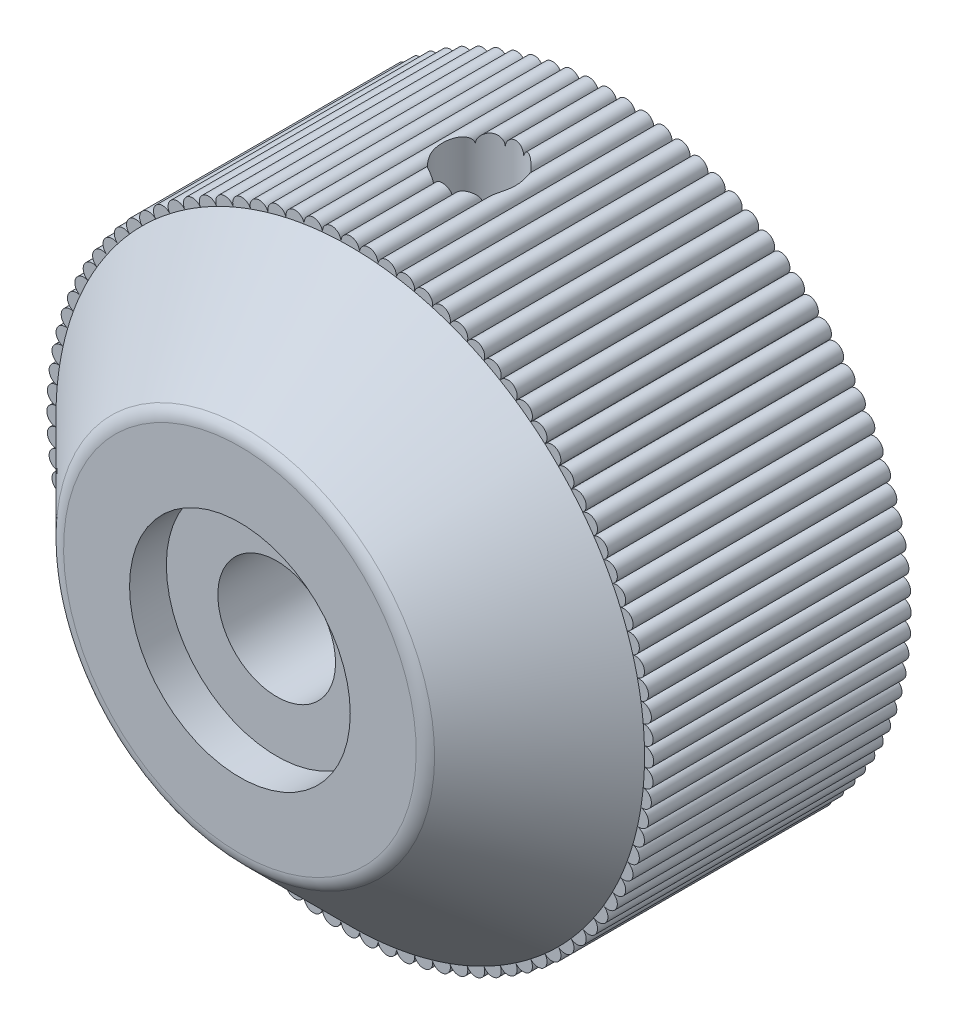
SolidWorks part; units mm, degrees
ref_plane "Front Plane" through (0, 0, 0) normal (0, 0, 1) x (1, 0, 0)
ref_plane "Top Plane" through (0, 0, 0) normal (0, 1, 0) x (1, 0, 0)
ref_plane "Right Plane" through (0, 0, 0) normal (1, 0, 0) x (0, 0, -1)
sketch "Main Body Sketch" plane through (0, 0, 0) normal (1, 0, 0) x (0, 0, -1)
  line L0 (0, 0) -> (-10, 0)
  line L1 (-10, 0) -> (-10, 5)
  line L2 (-10, 5) -> (-7, 8)
  line L4 (-7, 8) -> (0, 8)
  line L5 (0, 8) -> (0, 0)
  dimension "D1" = 5
  dimension "D2" = 8
  dimension "D3" = 10
  dimension "D4" = 7
revolve "Main Body Revolve" add sketch "Main Body Sketch" angle 360 about L0
sketch "Grip Sketch" plane through (0, 0, 0) normal (0, 0, -1) x (-1, 0, 0)
  circle A0 centre (0, 8) radius 0.25
  circle A1 centre (0, 0) radius 8 construction
  dimension "D1" = 0.5
extrude "Grip Extrude" add sketch "Grip Sketch" against normal blind 7
pattern_circular "Grip Circular Pattern" count 100 over 360 about axis through (0, 0, 0) along (0, 0, -1) of "Grip Extrude"
sketch "Fastener Pin Bore Sketch" plane through (0, 0, 0) normal (0, 1, 0) x (1, 0, 0)
  circle A0 centre (0, -3.5) radius 1
  dimension "D1" = 2
  dimension "D2" = 3.5
extrude "Fastener Pin Bore Extrude" cut sketch "Fastener Pin Bore Sketch" along normal up to next and the other way blind 5
sketch "Screw Head Housing Sketch" plane through (0, 0, 10) normal (0, 0, 1) x (1, 0, 0)
  circle A0 centre (0, 0) radius 3
  dimension "D1" = 6
extrude "Screw Head Housing Extrude" cut sketch "Screw Head Housing Sketch" against normal blind 1
sketch "Screw Bore Hole Sketch" plane through (0, 0, 9) normal (0, 0, 1) x (1, 0, 0)
  circle A0 centre (0, 0) radius 1.6
  dimension "D1" = 3.2
extrude "Screw Bore Hole Extrude" cut sketch "Screw Bore Hole Sketch" against normal up to next
fillet "Front Fillet" radius 0.5 1 edges at (0, 5, 10)
